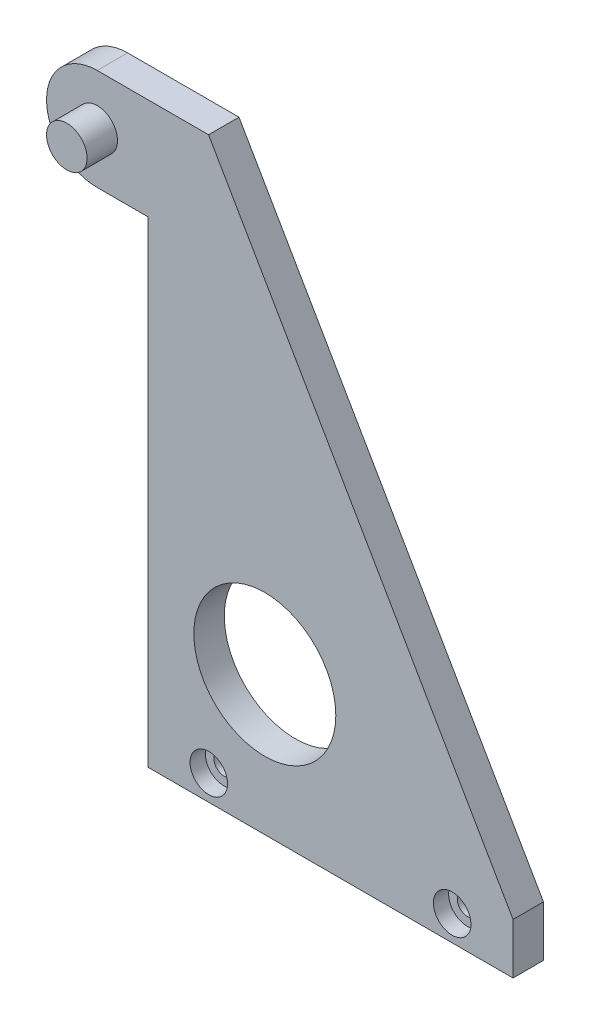
SolidWorks part; units mm, degrees
ref_plane "前视基准面" through (0, 0, 0) normal (0, 0, 1) x (1, 0, 0)
ref_plane "上视基准面" through (0, 0, 0) normal (0, 1, 0) x (1, 0, 0)
ref_plane "右视基准面" through (0, 0, 0) normal (1, 0, 0) x (0, 0, -1)
sketch "草图1" plane through (0, 0, 0) normal (0, 0, 1) x (1, 0, 0)
  line L0 (-18, 0) -> (18, 0)
  line L1 (18, 0) -> (18, 5)
  line L2 (18, 5) -> (-12.0222, 57)
  line L3 (-12.0222, 57) -> (-28, 57)
  line L4 (-28, 57) -> (-28, 47)
  line L5 (-28, 47) -> (-18, 47)
  line L6 (-18, 47) -> (-18, 0)
  point P3 (-28, 52)
  point P4 (0, 0)
  point P10 (-12.5618, 57)
  point P11 (-5.6077, 57)
  dimension "D1" = 36
  dimension "D2" = 5
  dimension "D3" = 10
  dimension "D4" = 47
  dimension "D5" = 120
extrude "凸台-拉伸1" add sketch "草图1" along normal blind 3
sketch "草图3" plane through (0, 0, 3) normal (0, 0, 1) x (1, 0, 0)
  circle A0 centre (-6.4764, 13.6875) radius 7
  dimension "D1" = 14
extrude "切除-拉伸1" cut sketch "草图3" against normal through all
sketch "草图4" plane through (0, 0, 3) normal (0, 0, 1) x (1, 0, 0)
  line L0 (-18, 5) -> (18, 0) construction
  line L1 (-18, 0) -> (18, 0) construction
  line L2 (-18, 0) -> (-18, 5) construction
  line L3 (-18, 5) -> (18, 5) construction
  line L4 (18, 0) -> (18, 5) construction
  line L5 (18, 5) -> (-18, 0) construction
  line L6 (-1000, 2.5) -> (49000, 2.5) construction
  line L7 (0, -997.5) -> (0, 49002.5) construction
  circle A0 centre (12, 2.5) radius 1
  circle A1 centre (-12, 2.5) radius 1
  point P9 (0, 2.5)
  dimension "D1" = 2
  dimension "D2" = 12
extrude "切除-拉伸2" cut sketch "草图4" against normal through all
sketch "草图5" plane through (0, 0, 3) normal (0, 0, 1) x (1, 0, 0)
  line L0 (-28, 57) -> (-18, 47) construction
  line L1 (-28, 57) -> (-18, 57) construction
  line L2 (-28, 57) -> (-28, 47) construction
  line L3 (-28, 47) -> (-18, 47) construction
  line L4 (-18, 57) -> (-18, 47) construction
  line L5 (-28, 47) -> (-18, 57) construction
  circle A0 centre (-23, 52) radius 2
  dimension "D1" = 4
extrude "凸台-拉伸2" add sketch "草图5" along normal blind 3
fillet "圆角1" 2 edges at (-28, 57, 1.5) (-28, 47, 1.5) type full round first side face at (-20.0111, 57, 1.5) second side face at (-23, 47, 1.5) middle face at (-28, 52, 1.5)
sketch "草图6" plane through (0, 0, 3) normal (0, 0, 1) x (1, 0, 0)
  circle A0 centre (12, 2.5) radius 1.85
  circle A1 centre (-12, 2.5) radius 1.85
  dimension "D1" = 3.7
extrude "切除-拉伸3" cut sketch "草图6" against normal blind 1.5
